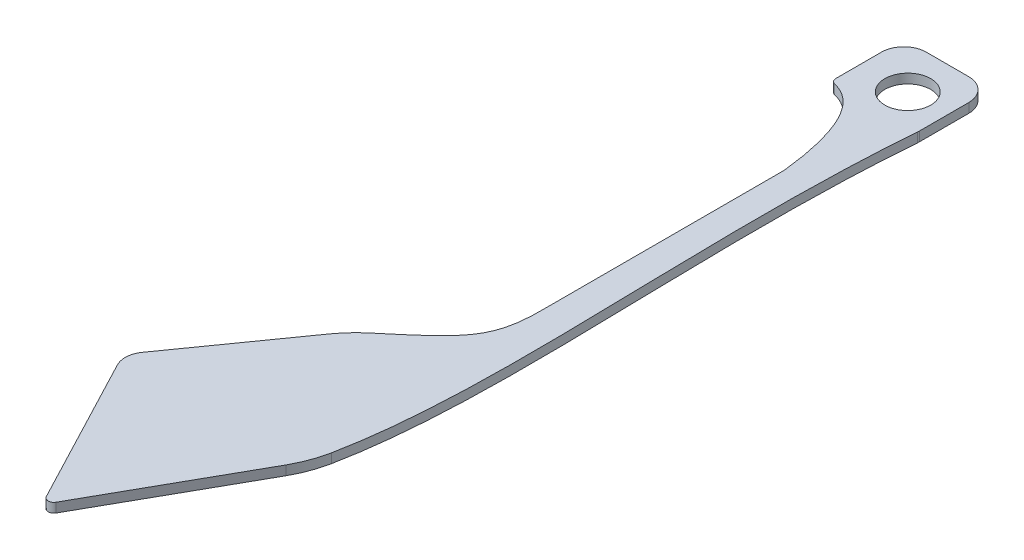
SolidWorks part; units mm, degrees
ref_plane "Front Plane" through (0, 0, 0) normal (0, 0, 1) x (1, 0, 0)
ref_plane "Top Plane" through (0, 0, 0) normal (0, 1, 0) x (1, 0, 0)
ref_plane "Right Plane" through (0, 0, 0) normal (1, 0, 0) x (0, 0, -1)
sketch "Sketch1" plane through (0, 0, 0) normal (0, 1, 0) x (1, 0, 0)
  line L0 (2.5, 68) -> (2.5, 74.5)
  line L1 (2.5, 74.5) -> (10.3, 74.5)
  line L2 (10.3, 74.5) -> (10.3, 68)
  line L3 (-8, 15.25) -> (0, 0)
  line L4 (0, 0) -> (8.5645, 15.25)
  line L5 (7.3, 59) -> (7.3, 38)
  line L6 (-8, 15.25) -> (0.3828, 27.0812)
  spline S0 degree 2 poles (2.5, 68) (6.3647, 67.5769) (7.3, 59) knots 0 0 0 1 1 1
  spline S1 degree 3 poles (10.3, 68) (8.7144, 49.1108) (11.8169, 28.4826) (8.5645, 15.25) knots 0 0 0 0 1 1 1 1
  spline S2 degree 3 poles (7.3, 38) (7.4007, 32.6745) (6.1471, 31.91) (0.3828, 27.0812) knots 0 0 0 0 1 1 1 1
  point P8 (-22.6524, -32.0806)
  point P10 (-16.4399, -59.7778)
  point P12 (-17.7368, -58.4259)
  dimension "D13" = 15.3
  dimension "D1" = 6.5
  dimension "D2" = 7.8
  dimension "D3" = 57
  dimension "D4" = 8
  dimension "D5" = 15.25
  dimension "D6" = 16.5645
  dimension "D7" = 21
  dimension "D8" = 3
  dimension "D9" = 14.5
  dimension "D10" = 117
  dimension "D11" = 74.5
  dimension "D12" = 38
extrude "Boss-Extrude1" add sketch "Sketch1" along normal mid plane 0.84
sketch "Sketch2" plane through (0, 0.42, 0) normal (0, 1, 0) x (1, 0, 0)
  line L0 (10.3, 74.5) -> (2.5, 74.5) construction
  line L1 (10.3, 68) -> (10.3, 74.5) construction
  circle A0 centre (6.75, 70.6) radius 2.05
  dimension "D1" = 4.1
  dimension "D2" = 3.9
  dimension "D3" = 3.55
extrude "Cut-Extrude1" cut sketch "Sketch2" against normal through all
fillet "Fillet1" radius 10 2 edges at (8.5645, 0, -15.25) (0.3828, 0, -27.0812)
fillet "Fillet2" radius 0.5 1 edges at (2.5, 0, -68)
fillet "Fillet3" radius 2 2 edges at (2.5, 0, -74.5) (10.3, 0, -74.5)
fillet "Fillet4" radius 2 1 edges at (-8, 0, -15.25)
fillet "Fillet5" radius 0.5 1 edges at (0, 0, 0)
fillet "Fillet6" radius 2 3 edges at (7.3, 0, -38) (7.3, 0, -59) (10.3, 0, -68)
equation "\"D2@Sketch2\"=1.85+\"D1@Sketch2\"/2"
equation "\"D3@Sketch2\"=1.5 +\"D1@Sketch2\"/2"
